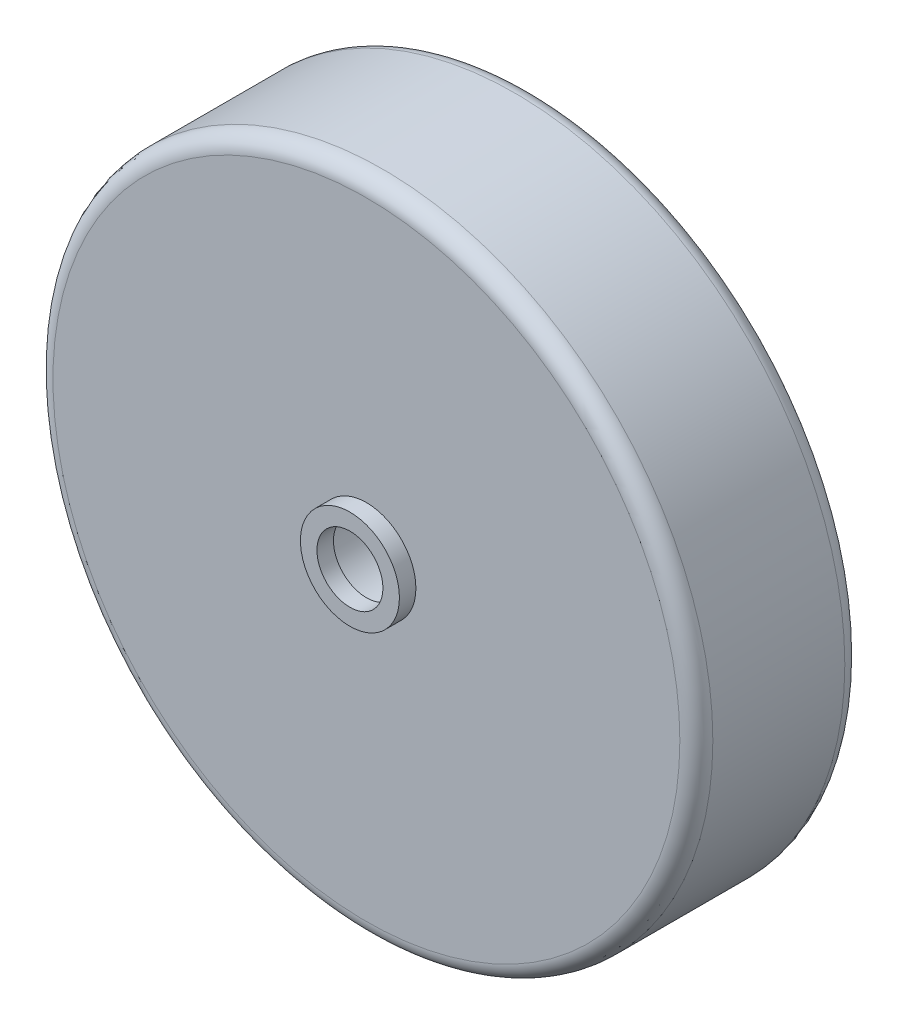
SolidWorks part; units mm, degrees
material "Rubber"
ref_plane "Front Plane" through (0, 0, 0) normal (0, 0, 1) x (1, 0, 0)
ref_plane "Top Plane" through (0, 0, 0) normal (0, 1, 0) x (1, 0, 0)
ref_plane "Right Plane" through (0, 0, 0) normal (1, 0, 0) x (0, 0, -1)
sketch "Sketch1" plane through (0, 0, 0) normal (0, 0, 1) x (1, 0, 0)
  circle A0 centre (0, 0) radius 100
  circle A1 centre (0, 0) radius 10
  circle A2 centre (0, 0) radius 15
  dimension "D1" = 200
  dimension "D2" = 20
  dimension "D3" = 5
extrude "Boss-Extrude1" add sketch "Sketch1" along normal blind 50 contours A0 A1 region at (-97.1716, 0, 0)
fillet "Fillet1" radius 5 2 edges at (100, 0, 0) (100, 0, 50)
extrude "Boss-Extrude2" add sketch "Sketch1<5>" against normal blind 5 separate body contours A2 A1 region at (-14.5757, 0, 0)
sketch "Sketch1<5>" plane through (0, 0, 0) normal (0, 0, 1) x (1, 0, 0) same geometry as "Sketch1"
extrude "Boss-Extrude3" add sketch "Sketch1<6>" along normal blind 5 from surface separate body contours A2 A1 region at (-14.5757, 0, 0) starting at face at (95, 0, 50)
sketch "Sketch1<6>" plane through (0, 0, 0) normal (0, 0, 1) x (1, 0, 0) same geometry as "Sketch1"
